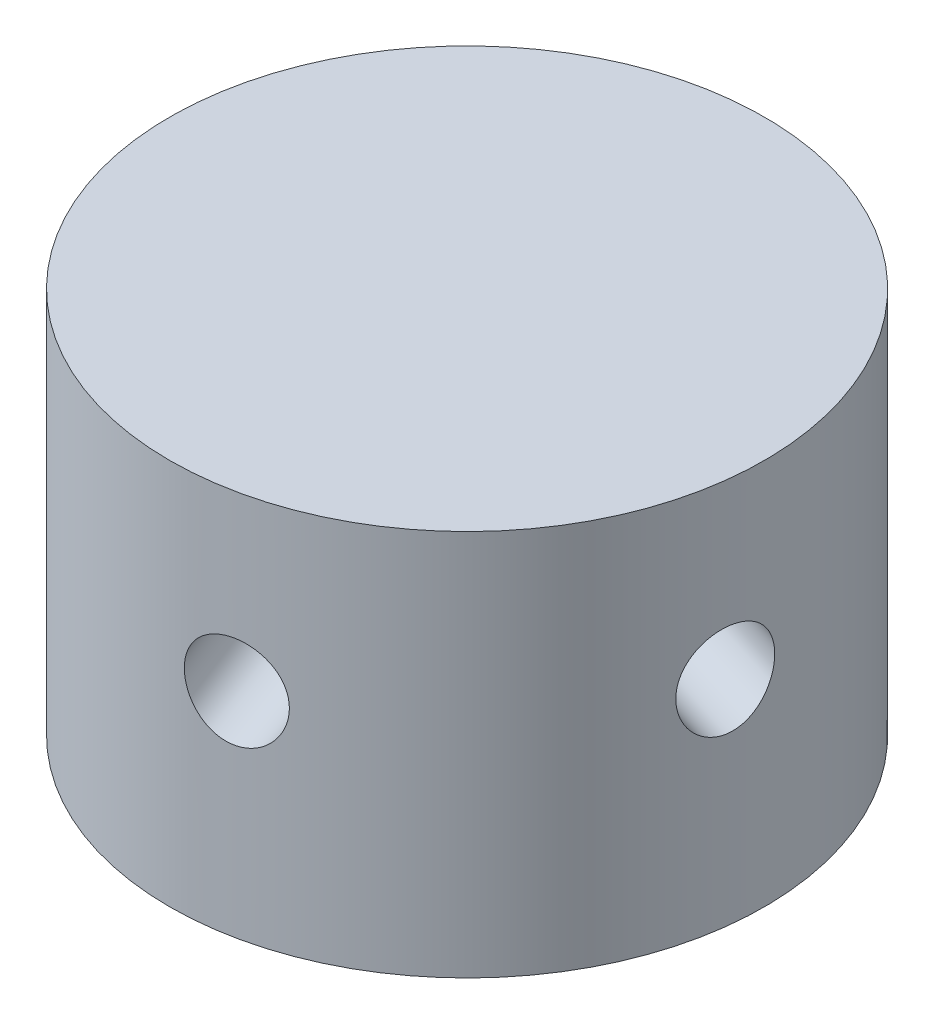
SolidWorks part; units mm, degrees
ref_plane "Front Plane" through (0, 0, 0) normal (0, 0, 1) x (1, 0, 0)
ref_plane "Top Plane" through (0, 0, 0) normal (0, 1, 0) x (1, 0, 0)
ref_plane "Right Plane" through (0, 0, 0) normal (1, 0, 0) x (0, 0, -1)
sketch "Sketch1" plane through (0, 0, 0) normal (0, 1, 0) x (1, 0, 0)
  circle A0 centre (0, 0) radius 10
  dimension "D1" = 20
extrude "Boss-Extrude1" add sketch "Sketch1" along normal blind 3 and the other way blind 10
ref_axis "5hubaxis" through (0, 5.5, 0) along (0, -1, 0)
ref_plane "holeplane" through (-3.3529, -1.0931, 1.8877) normal (0.8382, 0.2733, -0.4719) x (-0.4487, -0.1463, -0.8816)
sketch "Sketch4" plane through (-3.3529, -1.0931, 1.8877) normal (0.8382, 0.2733, -0.4719) x (-0.4487, -0.1463, -0.8816)
  circle A0 centre (0, 0) radius 1.5 construction
  circle A1 centre (0, 0) radius 1.5
extrude "hole" cut sketch "Sketch4" against normal through all
pattern_circular "holecir" count 5 over 360 about axis through (0, 5.5, 0) along (0, -1, 0) of "hole"
sketch "Sketch5" plane through (0, -10, 0) normal (0, -1, 0) x (1, 0, 0)
  line L0 (-10, 0) -> (10, 0) construction
  circle A0 centre (0, 0) radius 10 construction
  text T0 "5"
extrude "Boss-Extrude2" [suppressed] add sketch "Sketch5" along normal blind 1
ref_plane "Plane1" through (0, -5, 0) normal (0, -1, 0) x (-1, 0, 0)
sketch "Sketch6" plane through (0, -5, 0) normal (0, -1, 0) x (-1, 0, 0)
  circle A0 centre (0, 0) radius 3
  dimension "D1" = 6
extrude "bearinghole" cut sketch "Sketch6" against normal mid plane 2.5
sketch "Sketch7" plane through (0, -5, 0) normal (0, -1, 0) x (-1, 0, 0)
  circle A0 centre (0, 0) radius 1.5
  dimension "D1" = 3
extrude "shafthole" cut sketch "Sketch7" along normal through all
sketch "Sketch8" plane through (0, -10, 0) normal (0, -1, 0) x (1, 0, 0)
  line L0 (-9.648, 2.6298) -> (9.648, 2.6298) construction
  circle A1 centre (0, 0) radius 10 construction
  text T0 "5-axis"
  point P2 (-9.6905, 2.4688)
  point P6 (9.648, 2.6298)
extrude "Boss-Extrude3" add sketch "Sketch8" along normal blind 1
